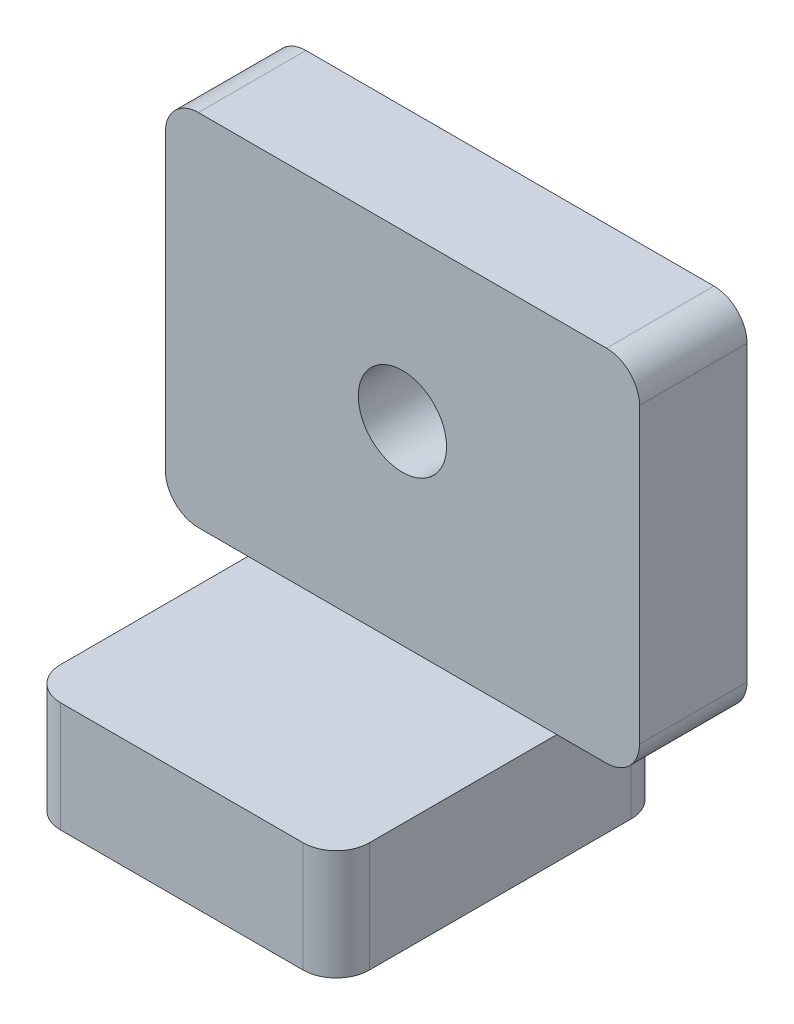
SolidWorks part; units mm, degrees
ref_plane "Front Plane" through (0, 0, 0) normal (0, 0, 1) x (1, 0, 0)
ref_plane "Top Plane" through (0, 0, 0) normal (0, 1, 0) x (1, 0, 0)
ref_plane "Right Plane" through (0, 0, 0) normal (1, 0, 0) x (0, 0, -1)
sketch "Sketch1" plane through (0, 0, 0) normal (0, 0, 1) x (1, 0, 0)
  line L1 (-21.5, -16.3) -> (21.5, -16.3)
  line L2 (-21.5, -16.3) -> (-21.5, 16.3)
  line L3 (-21.5, 16.3) -> (21.5, 16.3)
  line L4 (21.5, -16.3) -> (21.5, 16.3)
  line L5 (-21.5, -16.3) -> (21.5, 16.3) construction
  line L6 (-21.5, 16.3) -> (21.5, -16.3) construction
  point P0 (0, 0)
  dimension "D1" = 43
  dimension "D2" = 32.6
extrude "Boss-Extrude1" add sketch "Sketch1" along normal mid plane 9.75
sketch "Sketch2" plane through (0, 0, 4.875) normal (0, 0, 1) x (1, 0, 0)
  line L0 (0, 1.3) -> (0, -16.3) construction
  line L9 (21.5, 16.3) -> (-21.5, 16.3) construction
  line L10 (-21.5, -16.3) -> (21.5, -16.3) construction
  circle A4 centre (0, 1.3) radius 4
  point P13 (0, 1.3)
  dimension "D5" = 8
  dimension "D2" = 15
extrude "Cut-Extrude1" cut sketch "Sketch2" against normal through all
sketch "Sketch3" plane through (0, 0, 4.875) normal (0, 0, 1) x (1, 0, 0)
  line L0 (-14, -16.3) -> (-14, -26.3)
  line L1 (-21.5, -16.3) -> (21.5, -16.3) construction
  line L2 (-14, -26.3) -> (14, -26.3)
  line L3 (14, -26.3) -> (14, -16.3)
  line L4 (14, -16.3) -> (-14, -16.3)
  line L5 (0, 0) -> (0, -16.3) construction
  dimension "D1" = 28
  dimension "D2" = 10
extrude "Boss-Extrude3" add sketch "Sketch3" against normal up to surface (9.75 mm away) and the other way blind 20 up to face at (4, 1.3, -4.875)
fillet "Fillet1" radius 3 8 edges at (21.5, -16.3, 0) (-21.5, -16.3, 0) (-21.5, 16.3, 0) (21.5, 16.3, 0) (-14, -21.3, -4.875) (14, -21.3, -4.875) (14, -21.3, 24.875) (-14, -21.3, 24.875)
